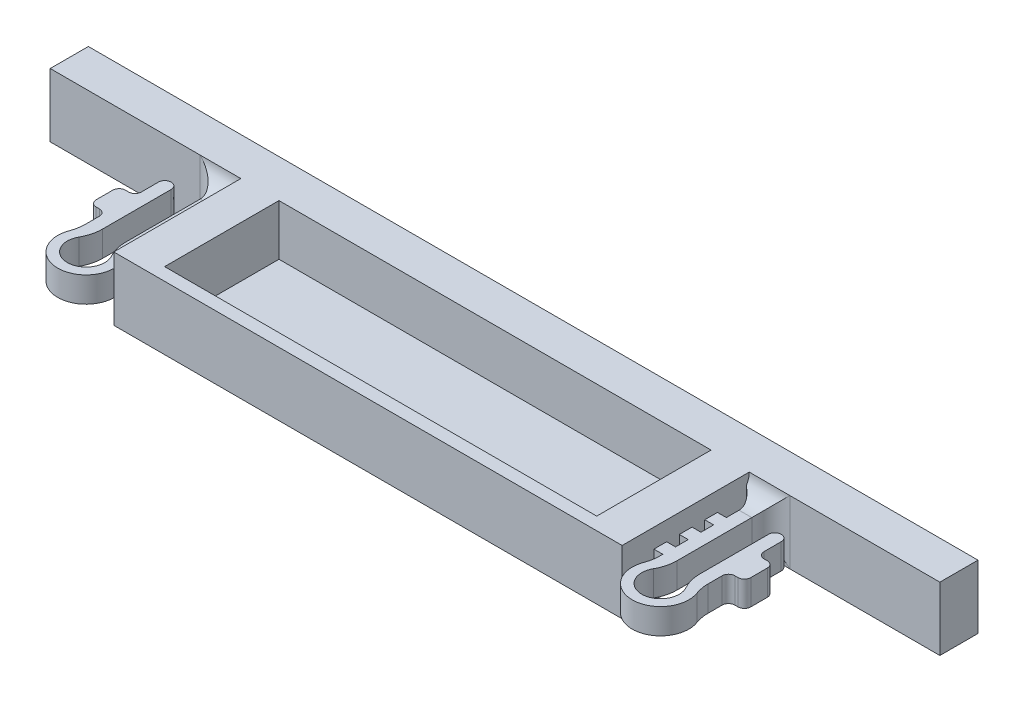
SolidWorks part; units mm, degrees
ref_plane "Front Plane" through (0, 0, 0) normal (0, 0, 1) x (1, 0, 0)
ref_plane "Top Plane" through (0, 0, 0) normal (0, 1, 0) x (1, 0, 0)
ref_plane "Right Plane" through (0, 0, 0) normal (1, 0, 0) x (0, 0, -1)
sketch "Sketch1" plane through (0, 0, 0) normal (0, 1, 0) x (1, 0, 0)
  line L1 (-88.9, 16.51) -> (88.9, 16.51)
  line L2 (-88.9, 16.51) -> (-88.9, -16.51)
  line L3 (-88.9, -16.51) -> (88.9, -16.51)
  line L4 (88.9, 16.51) -> (88.9, -16.51)
  line L5 (-88.9, 16.51) -> (88.9, -16.51) construction
  line L6 (-88.9, -16.51) -> (88.9, 16.51) construction
  line L7 (-88.9, -16.51) -> (-63.5, -16.51)
  line L8 (-88.9, -16.51) -> (-88.9, 8.89)
  line L9 (-88.9, 8.89) -> (-63.5, 8.89)
  line L10 (-63.5, -16.51) -> (-63.5, 8.89)
  line L11 (88.9, -16.51) -> (63.5, -16.51)
  line L12 (88.9, -16.51) -> (88.9, 8.89)
  line L13 (88.9, 8.89) -> (63.5, 8.89)
  line L14 (63.5, -16.51) -> (63.5, 8.89)
  point P0 (0, 0)
  dimension "D1" = 33.02
  dimension "D2" = 177.8
  dimension "D3" = 25.4
  dimension "D4" = 25.4
extrude "Boss-Extrude1" add sketch "Sketch1" along normal blind 12.7 contours L3 L14 L13 L4 L1 L2 L9 L10
sketch "Sketch6" plane through (0, 12.7, 0) normal (0, 1, 0) x (1, 0, 0)
  line L0 (-63.5, -16.51) -> (-63.5, 8.89) construction
  line L1 (-43.18, 8.89) -> (43.18, 8.89)
  line L2 (-43.18, 8.89) -> (-43.18, -13.97)
  line L3 (-43.18, -13.97) -> (43.18, -13.97)
  line L4 (43.18, 8.89) -> (43.18, -13.97)
  line L5 (-43.18, 8.89) -> (43.18, -13.97) construction
  line L6 (-43.18, -13.97) -> (43.18, 8.89) construction
  line L9 (63.5, -16.51) -> (63.5, 8.89) construction
  line L10 (-88.9, 16.51) -> (88.9, 16.51) construction
  dimension "D1" = 20.32
  dimension "D2" = 20.32
  dimension "D3" = 22.86
  dimension "D4" = 7.62
extrude "Cut-Extrude3" cut sketch "Sketch6" against normal blind 10.16
sketch "Sketch7" plane through (0, 12.7, 0) normal (0, 1, 0) x (1, 0, 0)
  line L1 (63.5, -16.51) -> (50.8, -16.51)
  line L2 (63.5, -16.51) -> (63.5, 8.89)
  line L3 (63.5, 8.89) -> (50.8, 8.89)
  line L4 (50.8, -16.51) -> (50.8, 8.89)
  line L5 (-63.5, -16.51) -> (-50.8, -16.51)
  line L6 (-63.5, -16.51) -> (-63.5, 8.89)
  line L7 (-63.5, 8.89) -> (-50.8, 8.89)
  line L8 (-50.8, -16.51) -> (-50.8, 8.89)
  dimension "D1" = 12.7
  dimension "D2" = 25.4
extrude "Cut-Extrude4" cut sketch "Sketch7" against normal blind 12.7
sketch "Sketch14" plane through (0, 12.7, 0) normal (0, 1, 0) x (1, 0, 0)
  line L0 (-88.9, 16.51) -> (88.9, 16.51) construction
  line L1 (0, 16.51) -> (88.9, 16.51)
  line L2 (0, 16.51) -> (0, -16.51)
  line L3 (0, -16.51) -> (88.9, -16.51)
  line L4 (88.9, 16.51) -> (88.9, -16.51)
  line L5 (88.9, 16.51) -> (88.9, 8.89) construction
  line L6 (-50.8, -16.51) -> (50.8, -16.51) construction
  dimension "D1" = 88.9
extrude "Cut-Extrude5" cut sketch "Sketch14" against normal blind 19.558
sketch "Sketch15" plane through (0, 12.7, 0) normal (0, 1, 0) x (1, 0, 0)
  line L0 (-88.9, 16.51) -> (-88.9, 8.89) construction
  line L1 (-80.9141, 8.89) -> (-50.8, 8.89) construction
  line L2 (-55.118, 8.9026) -> (-52.578, 8.9026)
  line L3 (-55.118, 8.9026) -> (-55.118, -12.4735)
  line L4 (-55.118, -12.4735) -> (-52.578, -12.4735)
  line L5 (-52.578, 8.9026) -> (-52.578, -12.4735)
  line L6 (-62.23, -12.4735) -> (-62.23, 5.126)
  line L7 (-62.23, 5.126) -> (-59.69, 5.126)
  line L8 (-59.69, 5.126) -> (-59.69, -12.4735)
  line L11 (-62.23, -0.8378) -> (-65.405, -0.8378)
  line L12 (-62.23, -0.8378) -> (-62.23, -6.6798)
  line L13 (-62.23, -6.6798) -> (-65.405, -6.6798)
  line L14 (-65.405, -0.8378) -> (-65.405, -6.6798)
  arc A0 (-52.578, -12.4735) -> (-62.23, -12.4735) centre (-57.404, -15.4394) cw
  arc A1 (-59.69, -12.4735) -> (-55.118, -12.4735) centre (-57.404, -15.4394) ccw
  arc A2 (-59.69, -12.4735) -> (-50.8, 8.89) centre (-80.9141, 8.89) cw
  line M8 (-88.9, 8.89) -> (-50.8, 8.89)
  dimension "D1" = 26.67
  dimension "D2" = 2.54
  dimension "D3" = 2.54
  dimension "D4" = 3.175
  dimension "D5" = 5.842
  dimension "D6" = 21.3761
  dimension "D7" = 9.7278
  dimension "D8" = 3.764
  dimension "D9" = 4.572
extrude "Boss-Extrude2" add sketch "Sketch15" against normal blind 5.08 from offset 3.81 contours L5 L3 L4 M8 | A1 L8 L7 L6 A0 L4 | L12 L11 L14 L13 offset against normal yes
fillet "Fillet1" radius 7.62 4 edges at (-62.23, 6.35, 12.4735) (-52.578, 6.35, 12.4735) (-55.118, 6.35, 12.4735) (-59.69, 6.35, 12.4735)
fillet "Fillet2" radius 1.27 6 edges at (-62.23, 6.35, 6.6798) (-65.405, 6.35, 6.6798) (-65.405, 6.35, 0.8378) (-62.23, 6.35, 0.8378) (-59.69, 6.35, -5.126) (-62.23, 6.35, -5.126)
fillet "Fillet3" radius 3.81 4 edges at (-52.578, 6.35, -8.89) (-55.118, 6.35, -8.89) (-53.848, 3.81, -8.89) (-53.848, 8.89, -8.89)
sketch "Sketch16" plane through (0, 12.7, 0) normal (0, 1, 0) x (1, 0, 0)
  line L0 (-52.578, 5.08) -> (-52.578, -10.7944) construction
  line L1 (-52.578, 2.54) -> (-50.8, 2.54)
  line L2 (-52.578, 2.54) -> (-52.578, 0)
  line L3 (-52.578, 0) -> (-50.8, 0)
  line L4 (-50.8, 2.54) -> (-50.8, 0)
  line L5 (-50.8, -16.51) -> (-50.8, 8.89) construction
  line L6 (-52.578, 5.08) -> (-55.118, 5.08) construction
  line L7 (-52.578, -2.54) -> (-50.8, -2.54)
  line L8 (-52.578, -2.54) -> (-52.578, -5.08)
  line L9 (-52.578, -5.08) -> (-50.8, -5.08)
  line L10 (-50.8, -2.54) -> (-50.8, -5.08)
  line L11 (-52.578, -7.62) -> (-50.8, -7.62)
  line L12 (-52.578, -7.62) -> (-52.578, -10.16)
  line L13 (-52.578, -10.16) -> (-50.8, -10.16)
  line L14 (-50.8, -7.62) -> (-50.8, -10.16)
  dimension "D1" = 2.54
  dimension "D2" = 2.54
  dimension "D3" = 2.54
  dimension "D4" = 2.54
extrude "Boss-Extrude3" add sketch "Sketch16" against normal blind 5.08 from offset 3.81 offset against normal yes
mirror "Mirror1" about plane through (0, -6.858, -16.51) normal (-1, 0, 0) of bodies 118
